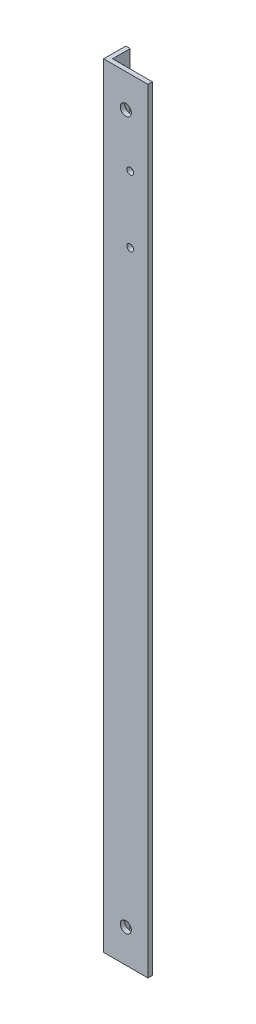
SolidWorks part; units mm, degrees
ref_plane "Front Plane" through (0, 0, 0) normal (0, 0, 1) x (1, 0, 0)
ref_plane "Top Plane" through (0, 0, 0) normal (0, 1, 0) x (1, 0, 0)
ref_plane "Right Plane" through (0, 0, 0) normal (1, 0, 0) x (0, 0, -1)
sketch "Sketch1" plane through (0, 0, 0) normal (0, 1, 0) x (1, 0, 0)
  line L0 (0, 0) -> (0, 10)
  line L1 (0, 10) -> (2, 10)
  line L2 (2, 10) -> (2, 2)
  line L3 (2, 2) -> (20, 2)
  line L4 (20, 2) -> (20, 0)
  line L5 (20, 0) -> (0, 0)
extrude "Boss-Extrude1" add sketch "Sketch1" along normal up to surface (350 mm away)
hole_wizard "Ø3.0 (3) Diameter Hole2" positions "Sketch4" profile "Sketch5" hole size "Ø3.0" standard "ISO"
sketch "Sketch4" plane through (0, -11.4076, -241.32) normal (-1, 0, 0) x (0, 0, 1)
  point P0 (235.32, 341.4076)
  point P2 (235.32, 355.4076)
sketch "Sketch5" plane through (0, 330, -6) normal (0, 1, 0) x (0, 0, 1)
  line L0 (0, 0) -> (0, 1.999)
  line L1 (0, 1.999) -> (1.5, 1.999)
  line L2 (1.5, 1.999) -> (1.5, 0)
  line L3 (1.5, 0) -> (0, 0)
  line L4 (0, -6.35) -> (0, 107.95) construction
  dimension "Thru Hole Dia." = 3
  dimension "Thru Hole Depth" = 1.999
hole_wizard "Ø3.0 (3) Diameter Hole4" positions "Sketch8" profile "Sketch9" hole size "Ø3.0" standard "ISO"
sketch "Sketch8" plane through (221.138, -11.4076, -2) normal (0, 0, -1) x (-1, 0, 0)
  point P0 (209.138, 293.4076)
  point P1 (209.138, 323.4076)
sketch "Sketch9" plane through (12, 282, -2) normal (1, 0, 0) x (0, 1, 0)
  line L0 (0, 0) -> (0, 1.999)
  line L1 (0, 1.999) -> (1.5, 1.999)
  line L2 (1.5, 1.999) -> (1.5, 0)
  line L3 (1.5, 0) -> (0, 0)
  line L4 (0, -6.35) -> (0, 107.95) construction
  dimension "Thru Hole Dia." = 3
  dimension "Thru Hole Depth" = 1.999
sketch "Sketch10" plane through (0, 0, 0) normal (0, 0, 1) x (1, 0, 0)
  line L0 (0, 0) -> (20, 0) construction
  line L1 (20, 350) -> (20, 0) construction
  line L2 (20, 350) -> (0, 350) construction
  circle A0 centre (10, 15) radius 2.5
  circle A1 centre (10, 335) radius 2.5
  dimension "D1" = 15
  dimension "D3" = 15
  dimension "D2" = 10
extrude "Cut-Extrude1" cut sketch "Sketch10" against normal through all
hole_wizard "Ø3.0 (3) Diameter Hole5" positions "Sketch11" profile "Sketch12" hole
sketch "Sketch11" plane through (0, -11.4076, -241.32) normal (-1, 0, 0) x (0, 0, 1)
  point P0 (235.32, 17.4076)
  point P1 (235.32, 31.4034)
sketch "Sketch12" plane through (0, 6, -6) normal (0, 1, 0) x (0, 0, 1)
  line L0 (0, 0) -> (0, 1.999)
  line L1 (0, 1.999) -> (1.5, 1.999)
  line L2 (1.5, 1.999) -> (1.5, 0)
  line L3 (1.5, 0) -> (0, 0)
  line L4 (0, -6.35) -> (0, 107.95) construction
  dimension "Thru Hole Dia." = 3
  dimension "Thru Hole Depth" = 1.999
